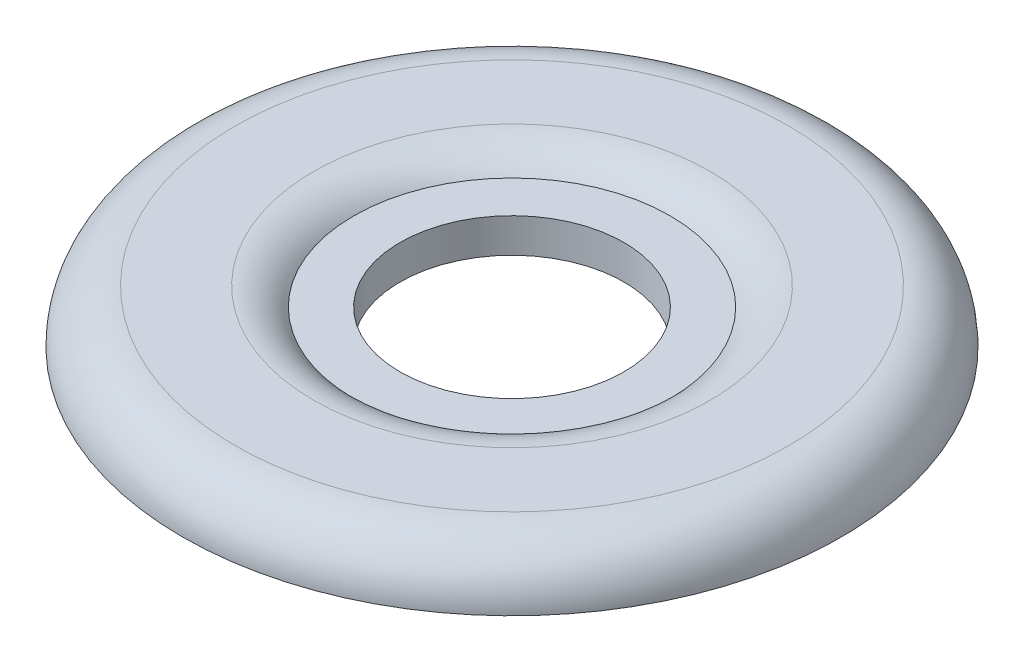
SolidWorks part; units mm, degrees
ref_plane "Front Plane" through (0, 0, 0) normal (0, 0, 1) x (1, 0, 0)
ref_plane "Top Plane" through (0, 0, 0) normal (0, 1, 0) x (1, 0, 0)
ref_plane "Right Plane" through (0, 0, 0) normal (1, 0, 0) x (0, 0, -1)
sketch "Sketch1" plane through (0, 0, 0) normal (0, 0, 1) x (1, 0, 0)
  line L0 (0, 0.3) -> (0, -1) construction
  line L1 (-12.5, -1) -> (12.5, -1)
  line L2 (-12.5, -1) -> (-12.5, 1)
  line L3 (-12.5, 1) -> (12.5, 1)
  line L4 (12.5, -1) -> (12.5, 1)
  line L5 (-12.5, -1) -> (12.5, 1) construction
  line L6 (-12.5, 1) -> (12.5, -1) construction
  line L7 (6, 1) -> (-6, 1)
  line L8 (6, 1) -> (6, 0.3)
  line L9 (6, 0.3) -> (-6, 0.3)
  line L10 (-6, 1) -> (-6, 0.3)
  line L12 (-4.25, -1) -> (4.25, -1)
  line L13 (-4.25, -1) -> (-4.25, 0.3)
  line L14 (-4.25, 0.3) -> (4.25, 0.3)
  line L15 (4.25, -1) -> (4.25, 0.3)
  line L16 (-4.25, -1) -> (4.25, 0.3) construction
  line L17 (-4.25, 0.3) -> (4.25, -1) construction
  line L18 (-11, -0.3) -> (-7, -0.3)
  line L19 (-11, -0.3) -> (-11, -1)
  line L20 (-11, -1) -> (-7, -1)
  line L21 (-7, -0.3) -> (-7, -1)
  line L22 (-11, -0.3) -> (-7, -1) construction
  line L23 (-11, -1) -> (-7, -0.3) construction
  point P0 (0, 0)
  point P12 (0, -0.35)
  point P17 (-9, -0.65)
  dimension "D1" = 25
  dimension "D2" = 12
  dimension "D3" = 2
  dimension "D4" = 1.3
  dimension "D5" = 8.5
  dimension "D6" = 4
  dimension "D7" = 1.3
  dimension "D8" = 9
revolve "Revolve1" add sketch "Sketch1" angle 360 about L0 region at (-8.5539, 0.0821, 0)
fillet "Fillet1" radius 2 4 edges at (0, 1, 12.5) (0, -0.3, 7) (0, -0.3, 11) (0, 1, 6)
